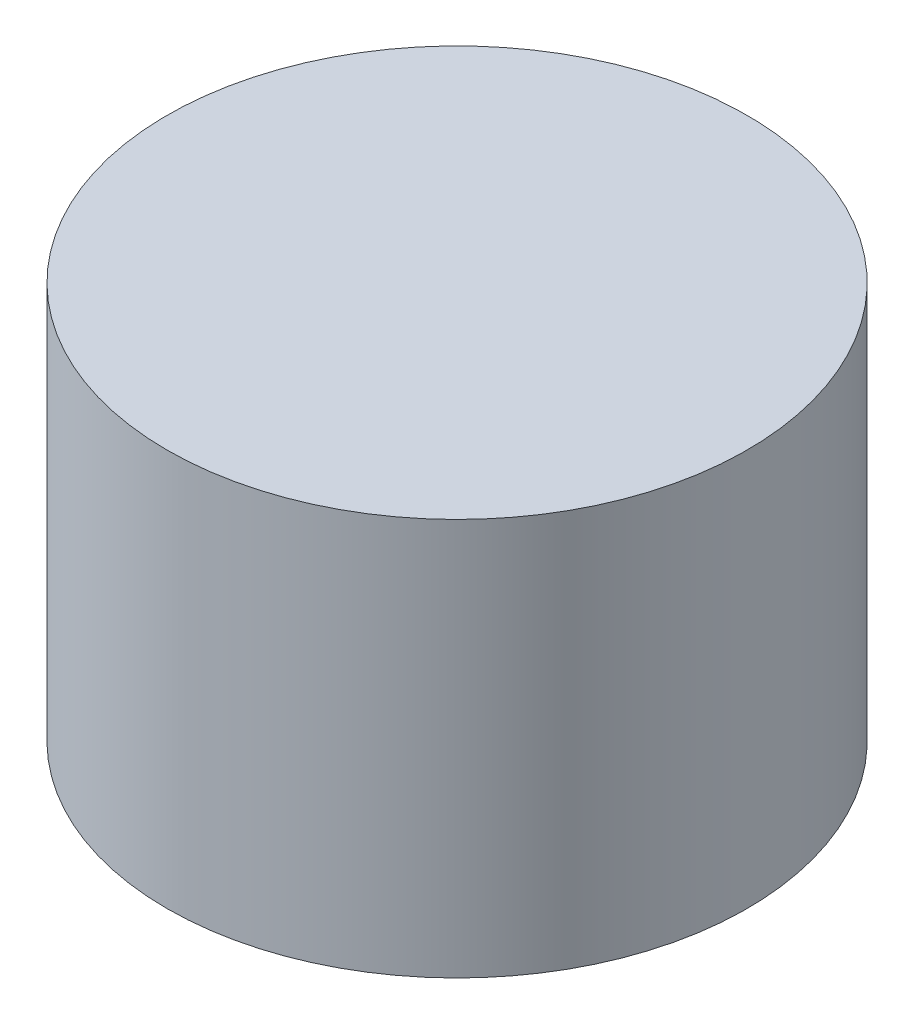
SolidWorks part; units mm, degrees
ref_plane "Front Plane" through (0, 0, 0) normal (0, 0, 1) x (1, 0, 0)
ref_plane "Top Plane" through (0, 0, 0) normal (0, 1, 0) x (1, 0, 0)
ref_plane "Right Plane" through (0, 0, 0) normal (1, 0, 0) x (0, 0, -1)
sketch "Sketch3" plane through (0, 0, 0) normal (0, 1, 0) x (1, 0, 0)
  circle A0 centre (0, 0) radius 23.075
  dimension "D1" = 46.15
extrude "Boss-Extrude3" add sketch "Sketch3" along normal blind 31.6
sketch "Sketch4" plane through (0, 0, 0) normal (0, -1, 0) x (1, 0, 0)
  circle A0 centre (0, 0) radius 22.075
  dimension "D1" = 44.15
extrude "Cut-Extrude1" cut sketch "Sketch4" against normal blind 30.6
